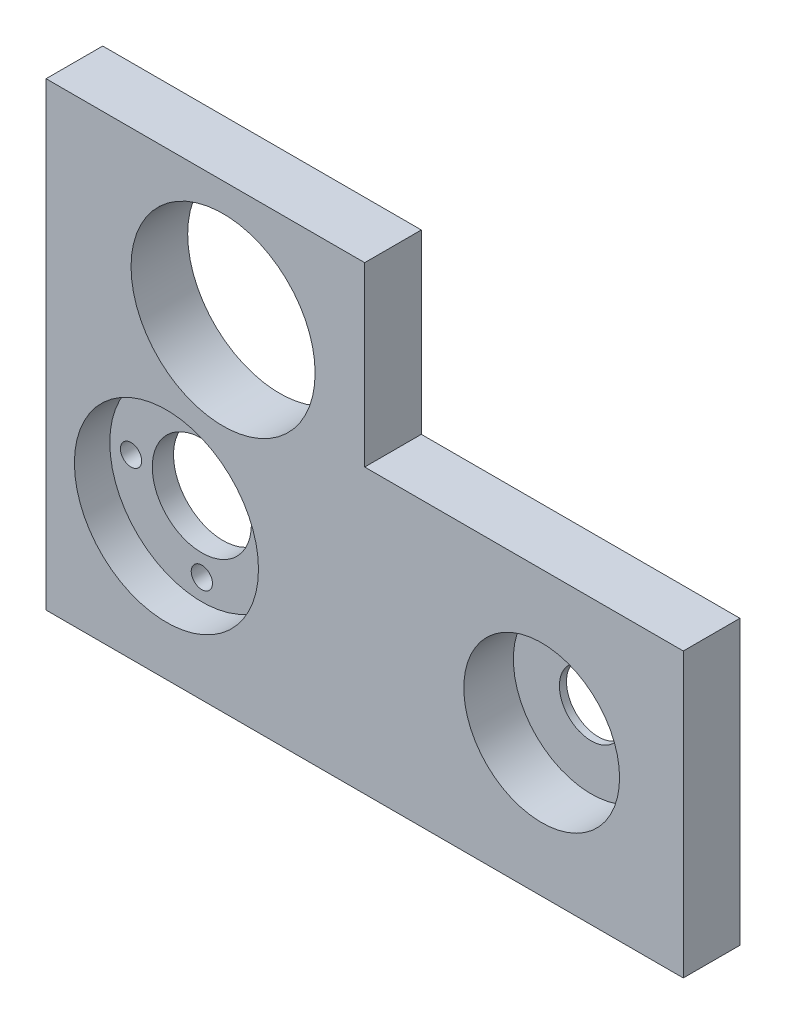
SolidWorks part; units mm, degrees
ref_plane "Front" through (0, 0, 0) normal (0, 0, 1) x (1, 0, 0)
ref_plane "Top" through (0, 0, 0) normal (0, 1, 0) x (1, 0, 0)
ref_plane "Right" through (0, 0, 0) normal (1, 0, 0) x (0, 0, -1)
sketch "Esquisse1" plane through (0, 0, 0) normal (0, 0, 1) x (1, 0, 0)
  line L1 (0, 0) -> (90, 0)
  line L2 (0, 0) -> (0, 65)
  line L3 (0, 65) -> (90, 65)
  line L4 (90, 0) -> (90, 65)
  circle A0 centre (70, 20) radius 4.5
  circle A1 centre (17, 20) radius 13
  circle A2 centre (25, 48) radius 13
  dimension "D3" = 9
  dimension "D4" = 20
  dimension "D6" = 53
  dimension "D8" = 26
  dimension "D9" = 26
  dimension "D1" = 90
  dimension "D2" = 65
  dimension "D5" = 70
  dimension "D7" = 20
  dimension "D10" = 53
  dimension "D11" = 48
extrude "Boss.-Extru.1" add sketch "Esquisse1" along normal blind 8
sketch "Esquisse2" plane through (0, 0, 0) normal (0, 0, -1) x (-1, 0, 0)
  circle A0 centre (-17, 20) radius 13
  circle A1 centre (-17, 20) radius 13 construction
extrude "Boss.-Extru.2" add sketch "Esquisse2" against normal blind 3
sketch "Esquisse3" plane through (0, 0, 3) normal (0, 0, 1) x (1, 0, 0)
  line L0 (27, 20) -> (17, 20) construction
  circle A0 centre (17, 20) radius 7
  circle A1 centre (27, 20) radius 1.5
  circle A2 centre (17, 10) radius 1.5
  circle A3 centre (7, 20) radius 1.5
  circle A4 centre (17, 30) radius 1.5
  point P5 (17.2364, 20)
  point P6 (0, 0)
  point P13 (17, 20)
  dimension "D1" = 14
  dimension "D2" = 3
  dimension "D3" = 10
  dimension "D4" = 4
extrude "Enlèv. mat.-Extru.1" cut sketch "Esquisse3" against normal through all
sketch "Esquisse4" plane through (0, 0, 8) normal (0, 0, 1) x (1, 0, 0)
  circle A0 centre (70, 20) radius 11
  point P2 (70, 25)
  dimension "D1" = 22
extrude "Enlèv. mat.-Extru.2" cut sketch "Esquisse4" against normal blind 7
sketch "Esquisse5" plane through (0, 0, 8) normal (0, 0, 1) x (1, 0, 0)
  line L0 (90, 65) -> (0, 65) construction
  line L1 (45, 65) -> (90, 65)
  line L2 (45, 65) -> (45, 40)
  line L3 (45, 40) -> (90, 40)
  line L4 (90, 65) -> (90, 40)
  line L5 (90, 0) -> (90, 65) construction
  dimension "D1" = 25
  dimension "D2" = 45
extrude "Enlèv. mat.-Extru.3" cut sketch "Esquisse5" against normal through all
